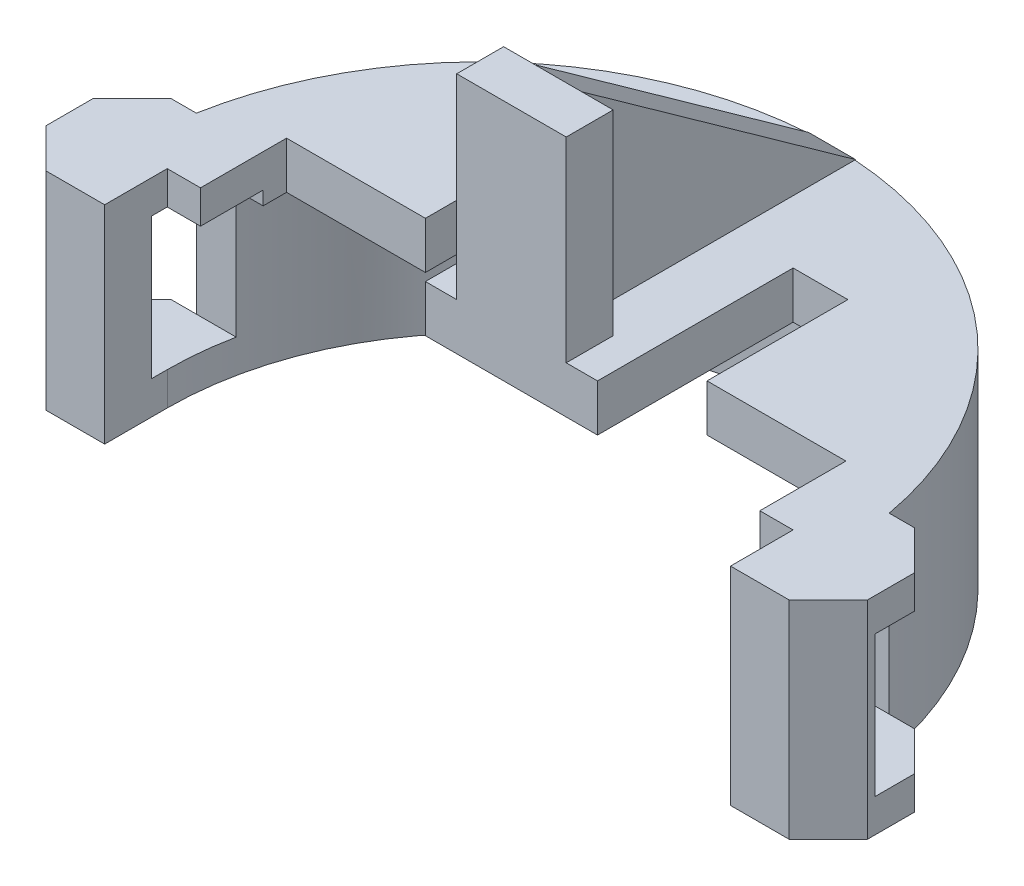
SolidWorks part; units mm, degrees
ref_plane "Front Plane" through (0, 0, 0) normal (0, 0, 1) x (1, 0, 0)
ref_plane "Top Plane" through (0, 0, 0) normal (0, 1, 0) x (1, 0, 0)
ref_plane "Right Plane" through (0, 0, 0) normal (1, 0, 0) x (0, 0, -1)
sketch "Sketch1" plane through (0, 0, 0) normal (0, 0, 1) x (1, 0, 0)
  line L0 (0, 0) -> (9, 0)
  line L1 (9, 0) -> (9, 5.3)
  line L2 (9, 5.3) -> (8, 5.3)
  line L3 (8, 5.3) -> (8, 0)
  line L4 (9, 4.1) -> (0, 4.1)
  line L5 (0, 4.1) -> (0, 5.3)
  line L6 (0, 5.3) -> (8, 5.3)
  line L7 (0, 0) -> (0, 2.65) construction
  dimension "D1" = 9
  dimension "D2" = 5.3
  dimension "D3" = 1
  dimension "D4" = 1.2
revolve "Revolve1" add sketch "Sketch1" angle 180 about L7 region at (8.5, 2.05, 0) region at (4, 4.7, 0) region at (8.5, 4.7, 0)
sketch "Sketch2" plane through (0, 0, 0) normal (0, 0, 1) x (1, 0, 0)
  line L0 (-8, 4.1) -> (8, 4.1) construction
  line L1 (-3.105, 4.1) -> (3.105, 4.1)
  line L2 (-3.105, 4.1) -> (-3.105, 2.6)
  line L3 (-3.105, 2.6) -> (3.105, 2.6)
  line L4 (3.105, 4.1) -> (3.105, 2.6)
  line L5 (-3.105, 4.1) -> (3.105, 2.6) construction
  line L6 (-3.105, 2.6) -> (3.105, 4.1) construction
  point P0 (0, 3.35)
  dimension "D1" = 6.21
  dimension "D2" = 1.5
  dimension "D3" = 0
  dimension "D4" = 0
extrude "Cut-Extrude1" cut sketch "Sketch2" against normal through all
sketch "Sketch3" plane through (0, 5.3, 0) normal (0, 1, 0) x (1, 0, 0)
  line L0 (9, 0) -> (-9, 0) construction
  line L1 (-3.6, 5.8) -> (3.6, 5.8)
  line L2 (-3.6, 5.8) -> (-3.6, 0)
  line L3 (-3.6, 0) -> (3.6, 0)
  line L4 (3.6, 5.8) -> (3.6, 0)
  line L5 (-3.6, 5.8) -> (3.6, 0) construction
  line L6 (-3.6, 0) -> (3.6, 5.8) construction
  line L8 (-2.2, 5.8) -> (2.2, 5.8)
  line L9 (-2.2, 5.8) -> (-2.2, 0.8)
  line L10 (-2.2, 0.8) -> (2.2, 0.8)
  line L11 (2.2, 5.8) -> (2.2, 0.8)
  line L12 (-2.2, 5.8) -> (2.2, 0.8) construction
  line L13 (-2.2, 0.8) -> (2.2, 5.8) construction
  point P0 (0, 2.9)
  point P8 (0, 3.3)
  line M9 (-9, 0) -> (9, 0)
  dimension "D1" = 7.2
  dimension "D2" = 5.8
  dimension "D3" = 0
  dimension "D4" = 0
  dimension "D5" = 4.4
  dimension "D6" = 5
  dimension "D7" = 0
  dimension "D8" = 0
extrude "Cut-Extrude2" cut sketch "Sketch3" against normal through all contours L1 L11 L10 L9 L2 L4 M9 region at (-2.9, 5.3, -5.7075)
sketch "Sketch4" plane through (0, 5.3, 0) normal (0, 1, 0) x (1, 0, 0)
  line L1 (3.6, 0) -> (7, 0)
  line L2 (3.6, 0) -> (3.6, -2)
  line L3 (3.6, -2) -> (7, -2)
  line L4 (7, 0) -> (7, -2)
  line L5 (-3.6, 0) -> (-7, 0)
  line L6 (-3.6, 0) -> (-3.6, -2)
  line L7 (-3.6, -2) -> (-7, -2)
  line L8 (-7, 0) -> (-7, -2)
  dimension "D1" = 3.4
  dimension "D2" = 3.4
  dimension "D3" = 2
  dimension "D4" = 2
extrude "Boss-Extrude1" add sketch "Sketch4" against normal blind 1.2
ref_plane "Plane1" through (8, 0, 0) normal (1, 0, 0) x (0, 0, -1)
sketch "Sketch5" plane through (8, 0, 0) normal (1, 0, 0) x (0, 0, -1)
  line L1 (1.6, 5.3) -> (-1.6, 5.3)
  line L2 (1.6, 5.3) -> (1.6, 0)
  line L3 (1.6, 0) -> (-1.6, 0)
  line L4 (-1.6, 5.3) -> (-1.6, 0)
  line L5 (-1.6, 5.3) -> (1.6, 0) construction
  line L6 (1.6, 5.3) -> (-1.6, 0) construction
  line L7 (0, 0) -> (0, 5.3) construction
  point P6 (0, 2.65)
  dimension "D1" = 2.65
  dimension "D2" = 5.3
  dimension "D3" = 3.2
  dimension "D4" = 0
sketch "Sketch6" plane through (0, 0, -0.8) normal (0, 0, 1) x (1, 0, 0)
  line L0 (-2.2, 5.3) -> (2.2, 5.3) construction
  line L1 (1.4, 5.3) -> (-1.4, 5.3)
  line L2 (1.4, 5.3) -> (1.4, 10.3)
  line L3 (1.4, 10.3) -> (-1.4, 10.3)
  line L4 (-1.4, 5.3) -> (-1.4, 10.3)
  line L5 (-1.4, 10.3) -> (1.4, 5.3) construction
  line L6 (-1.4, 5.3) -> (1.4, 10.3) construction
  point P6 (0, 7.8)
  dimension "D1" = 0
  dimension "D2" = 5
  dimension "D3" = 2.8
extrude "Boss-Extrude3" add sketch "Sketch6" against normal blind 1.2 contours L4 L3 L2 L1
sketch "Sketch7" plane through (0, 0, 0) normal (1, 0, 0) x (0, 0, -1)
  line L0 (2, 10.3) -> (9, 5.3)
  line L1 (9, 5.3) -> (0, 5.3) construction
  line L2 (9, 5.3) -> (2, 5.3)
  line L3 (2, 5.3) -> (2, 10.3)
extrude "Boss-Extrude4" add sketch "Sketch7" along normal mid plane 1.2
sketch "Sketch8" plane through (0, 5.3, 0) normal (0, 1, 0) x (1, 0, 0)
  line L1 (-7.15, 2.2) -> (7.15, 2.2)
  line L2 (-7.15, 2.2) -> (-7.15, 0)
  line L3 (-7.15, 0) -> (7.15, 0)
  line L4 (7.15, 2.2) -> (7.15, 0)
  line L5 (-7.15, 2.2) -> (7.15, 0) construction
  line L6 (-7.15, 0) -> (7.15, 2.2) construction
  line L7 (-2.5, 0) -> (2.5, 0)
  line L8 (-2.5, 0) -> (-2.5, 2.2)
  line L9 (-2.5, 2.2) -> (2.5, 2.2)
  line L10 (2.5, 0) -> (2.5, 2.2)
  line L11 (-2.5, 0) -> (2.5, 2.2) construction
  line L12 (-2.5, 2.2) -> (2.5, 0) construction
  line L13 (-7.15, 0) -> (9.555, 0)
  line L14 (-7.15, 0) -> (-7.15, -4.4024)
  line L15 (-7.15, -4.4024) -> (9.555, -4.4024)
  line L16 (9.555, 0) -> (9.555, -4.4024)
  point P0 (0, 1.1)
  point P5 (-7.15, 1.1)
  point P7 (0, 1.1)
  line M8 (-9, 0) -> (-7, 0)
  line M11 (-3.6, -2) -> (-3.6, 5.8)
  dimension "D1" = 0
  dimension "D2" = 0
  dimension "D3" = 2.2
  dimension "D4" = 14.3
  dimension "D5" = 5
  dimension "D6" = 16.705
  dimension "D7" = 4.4024
extrude "Cut-Extrude3" cut sketch "Sketch8" against normal blind 10 contours L3 L1 L2 M8 M11 | L10 L3 L4 L1 | L14 L13 L16 L15 region at (4.825, 5.3, -1.1) region at (-5.375, 5.3, -1.1)
extrude "Boss-Extrude5" add sketch "Sketch5" along normal blind 2.5 contours L4 L3 L2 L1
sketch "Sketch9" plane through (10.5, 0, 0) normal (1, 0, 0) x (0, 0, -1)
  line L0 (-1.6, 5.3) -> (1.6, 0) construction
  line L1 (-0.4, 4.45) -> (1.6, 4.45)
  line L2 (-0.4, 4.45) -> (-0.4, 0.85)
  line L3 (-0.4, 0.85) -> (1.6, 0.85)
  line L4 (1.6, 4.45) -> (1.6, 0.85)
  line L5 (-0.4, 4.45) -> (1.6, 0.85) construction
  line L6 (-0.4, 0.85) -> (1.6, 4.45) construction
  line L7 (1.6, 5.3) -> (-1.6, 0) construction
  line L8 (1.6, 5.3) -> (1.6, 0) construction
  line L9 (-1.6, 5.3) -> (-1.6, 0) construction
  point P0 (0.6, 2.65)
  point P15 (0, 2.65)
  dimension "D1" = 0
  dimension "D2" = 0
  dimension "D3" = 1.2
  dimension "D4" = 3.6
extrude "Cut-Extrude4" cut sketch "Sketch9" against normal blind 5
mirror "Mirror1" about plane through (0, 0, 0) normal (1, 0, 0) of "Boss-Extrude5", "Cut-Extrude4"
chamfer "Chamfer1" distance 1 angle 45 6 edges at (-10.5, 0.425, -1.6) (-10.5, 4.875, -1.6) (-10.5, 2.65, 1.6) (10.5, 0.425, -1.6) (10.5, 4.875, -1.6) (10.5, 2.65, 1.6)
